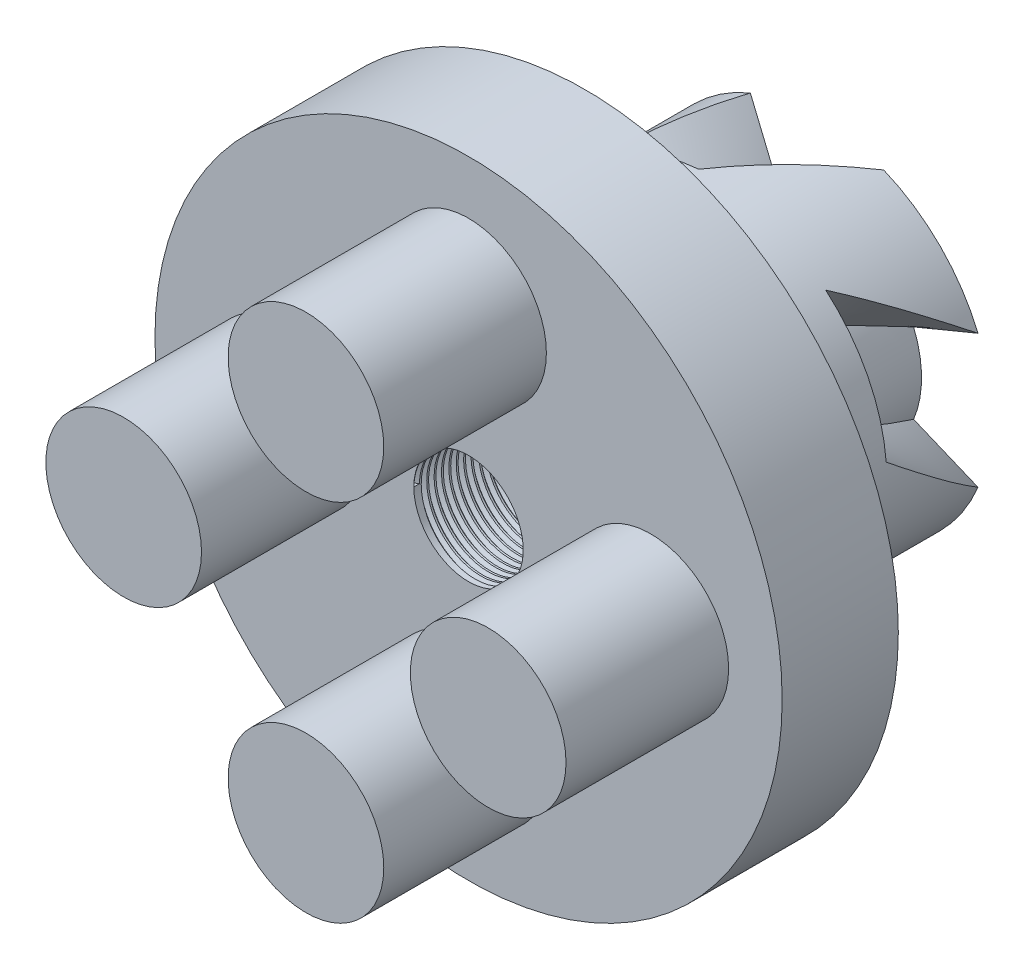
SolidWorks part; units mm, degrees
note: The reader was unsure of these and kept them because the rebuilt part matched: shared geometry of "Sketch2<3>".
ref_plane "Front Plane" through (0, 0, 0) normal (0, 0, 1) x (1, 0, 0)
ref_plane "Top Plane" through (0, 0, 0) normal (0, 1, 0) x (1, 0, 0)
ref_plane "Right Plane" through (0, 0, 0) normal (1, 0, 0) x (0, 0, -1)
sketch "Sketch2" plane through (0, 0, 0) normal (0, 0, 1) x (1, 0, 0)
  line L0 (0, 22.1469) -> (0, -16.8024) construction
  line L1 (-24.5572, 0) -> (20.0206, 0) construction
  circle A0 centre (0, 0) radius 13.5
  circle A1 centre (0, 7.845) radius 3.35
  circle A2 centre (7.845, 0) radius 3.35
  circle A3 centre (0, -7.845) radius 3.35
  circle A4 centre (-7.845, 0) radius 3.35
  point P9 (0, -16.8024)
  point P10 (0, 22.1469)
  point P11 (-24.5572, 0)
  point P18 (0, 0)
  point P19 (20.0206, 0)
  dimension "D1" = 27
  dimension "D2" = 6.7
  dimension "D4" = 7.845
  dimension "D3" = 4
extrude "Boss-Extrude1" add sketch "Sketch2" along normal blind 5 contours A4 | A1 | A2 | A3 | A0 A4 A3 A2 A1
extrude "Boss-Extrude2" add sketch "Sketch2<3>" along normal blind 12 contours A4 | A1 | A2 | A3
sketch "Sketch2<3>" plane through (0, 0, 0) normal (0, 0, 1) x (1, 0, 0) same geometry as "Sketch2"
sketch "Sketch3" plane through (0, 0, 0) normal (0, 0, -1) x (-1, 0, 0)
  circle A0 centre (0, 0) radius 2.355
  dimension "D1" = 4.71
extrude "Cut-Extrude1" cut sketch "Sketch3" against normal through all
sketch "Sketch4" plane through (0, 0, 0) normal (0, 0, -1) x (-1, 0, 0)
  line L0 (10.5816, 10.5816) -> (-11.9923, -11.9923) construction
  line L1 (-11.5627, 11.5627) -> (12.4016, -12.4016) construction
  line L2 (24.5572, 0) -> (-20.0206, 0) construction
  circle A0 centre (0, 0) radius 2.355
  circle A1 centre (0, 0) radius 7.5
  circle A2 centre (0, 0) radius 2.355 construction
  dimension "D3" = 15
  dimension "D1" = 90
  dimension "D2" = 45
extrude "Boss-Extrude3" add sketch "Sketch4" along normal blind 10
sketch "Sketch5" plane through (0, 0, -10) normal (0, 0, -1) x (-1, 0, 0)
  line L0 (0, 22.1469) -> (0, -16.8024) construction
  line L1 (-1.7221, 4.1575) -> (-2.8701, 6.9291)
  line L2 (2.8701, 6.9291) -> (1.7221, 4.1575)
  line L3 (0, 16.805) -> (0, -31.0259) construction
  arc A0 (-1.7221, 4.1575) -> (1.7221, 4.1575) centre (0, 0) cw
  arc A2 (-2.8701, 6.9291) -> (2.8701, 6.9291) centre (0, 0) cw
  circle A3 centre (0, 0) radius 7.5 construction
  circle A4 centre (0, 0) radius 7.5 construction
  point P8 (0, 7.5)
  dimension "D1" = 45
  dimension "D2" = 4.5
  dimension "D3" = 7.5
sketch "Sketch8" plane through (0, 0, -10) normal (0, 0, -1) x (-1, 0, 0)
  circle A0 centre (0, 0) radius 5
curve "Helix/Spiral1" pitch 60 height 4.5 turns 0.075
sweep "Cut-Sweep1" cut profiles "Sketch5" path "Helix/Spiral1"
pattern_circular "CirPattern1" count 4 over 360 about axis through (0, 0, 12) along (0, 0, -1) of "Cut-Sweep1"
thread "Thread1" pitch 0.3175 profile "Thread Profile1" start angle 0, offset 0, length 15, pitch 0.3175, diameter 4.71
ref_plane "Plane1" through (-2.355, 0, 5) normal (0, -1, 0) x (-1, 0, 0)
sketch "Thread Profile1" plane through (-2.355, 0, 5) normal (0, -1, 0) x (-1, 0, 0)
  line L0 (0, 0) -> (0, 0.3175) construction
  line L1 (0, 0) -> (0.1719, 0.0992)
  line L2 (0.1719, 0.0992) -> (0.1719, 0.1389)
  line L3 (0.1719, 0.1389) -> (0, 0.2381)
  line L4 (0.1719, 0.1191) -> (0, 0.1191) construction
  line L11 (0, 0) -> (0, 0.2381)
  point P2 (0, 0)
  dimension "Pitch" = 0.3175
  dimension "Profile_Angle" = 60
  dimension "Profile_Land" = 0.0397
  dimension "Profile_Height" = 0.1719
